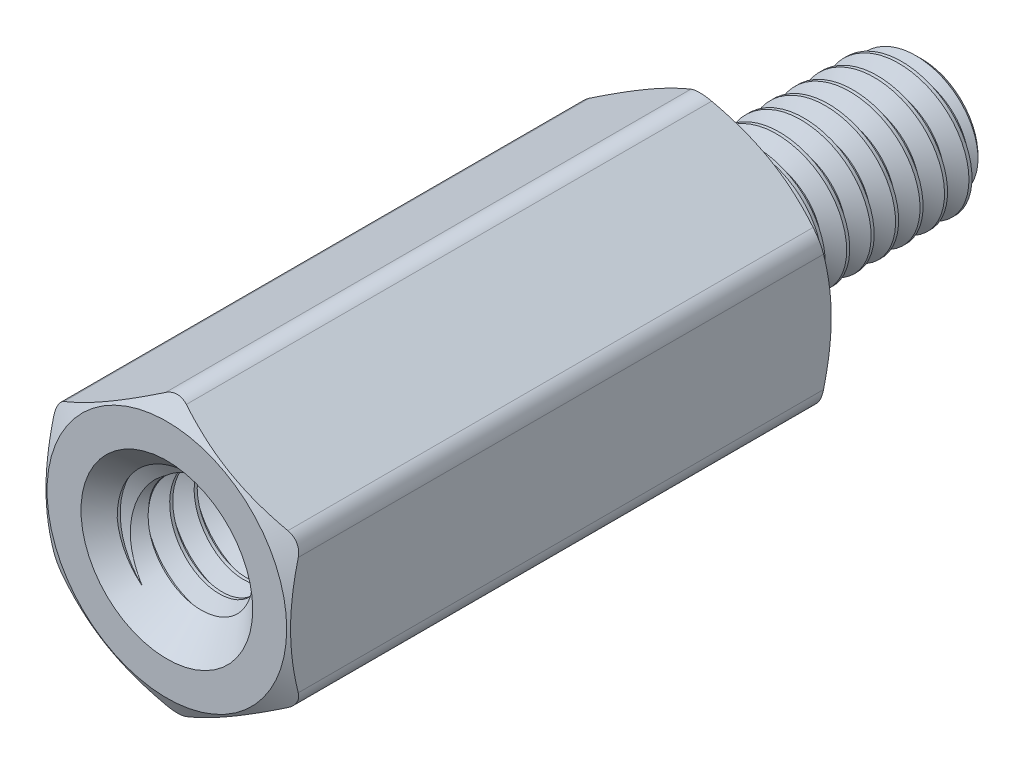
SolidWorks part; units mm, degrees
ref_plane "Front Plane" through (0, 0, 0) normal (0, 0, 1) x (1, 0, 0)
ref_plane "Top Plane" through (0, 0, 0) normal (0, 1, 0) x (1, 0, 0)
ref_plane "Right Plane" through (0, 0, 0) normal (1, 0, 0) x (0, 0, -1)
sketch "Sketch1" plane through (0, 0, 0) normal (0, 0, 1) x (1, 0, 0)
  line L1 (2.25, 1.299) -> (0, 2.5981)
  line L2 (0, 2.5981) -> (-2.25, 1.299)
  line L3 (-2.25, 1.299) -> (-2.25, -1.299)
  line L4 (-2.25, -1.299) -> (0, -2.5981)
  line L5 (0, -2.5981) -> (2.25, -1.299)
  line L6 (2.25, -1.299) -> (2.25, 1.299)
  circle A0 centre (0, 0) radius 2.25 construction
  point P10 (0, -2.25)
  dimension "Hex Size" = 4.5
sketch "Sketch2" plane through (0, 0, 0) normal (1, 0, 0) x (0, 0, -1)
  line L0 (3.9, 0) -> (-10, 0) construction
  line L2 (0, 1.25) -> (0, -1.25) construction
  line L3 (-5.2, 1.25) -> (-5.2, -1.25) construction
  line L4 (-10.4219, 1.2987) -> (-10.1969, 0.909) construction
  line L5 (-10.1969, 0.909) -> (-9.9719, 1.2987) construction
  line L6 (-9.9719, 1.2987) -> (-10.4219, 1.2987) construction
  line L7 (-10.3938, 1.25) -> (-10, 1.25) construction
  line L8 (-10.225, 0.9577) -> (-10.1688, 0.9577) construction
  line L9 (-10.1969, 0.9577) -> (-10.1969, 0.909) construction
  line L10 (-10.1969, 1.25) -> (-10.1969, 1.2987) construction
  line L11 (3.8719, 1.2987) -> (4.3219, 1.2987) construction
  line L12 (4.3219, 1.2987) -> (4.0969, 0.909) construction
  line L13 (4.0969, 0.909) -> (3.8719, 1.2987) construction
  line L14 (3.9, 1.25) -> (4.2937, 1.25) construction
  line L15 (4.0687, 0.9577) -> (4.125, 0.9577) construction
  line L16 (4.0969, 0.9577) -> (4.0969, 0.909) construction
  line L17 (4.0969, 1.25) -> (4.0969, 1.2987) construction
  line L18 (0, 2.5981) -> (-10, 2.5981) construction
  point P6 (0, 0)
  point P9 (-5.2, 0)
  dimension "Length" = 10
sketch "Sketch3" plane through (0, 0, 0) normal (1, 0, 0) x (0, 0, -1)
  line L0 (-5.2, 0) -> (3.9, 0)
  line L1 (-5.2, 1.25) -> (-5.2, -1.25) construction
  line L2 (3.9, 0) -> (3.9, 1.025)
  line L3 (3.9, 1.025) -> (3.675, 1.25)
  line L4 (3.675, 1.25) -> (0.6367, 1.25)
  line L5 (0.6367, 1.25) -> (0.468, 0.9577)
  line L6 (-5.2, 0) -> (-5.2, 1.025)
  line L7 (-5.2, 1.025) -> (-5.425, 1.25)
  line L8 (-5.425, 1.25) -> (-9.775, 1.25)
  line L9 (-9.775, 1.25) -> (-10, 1.475)
  line L10 (3.675, 0) -> (3.675, -1.25) construction
  line L11 (-10, 1.475) -> (-10, 2.25)
  line L12 (-10, 2.25) -> (0, 2.25)
  line L14 (0.468, 0.9577) -> (0.225, 0.9577)
  line L15 (0, 1.1827) -> (0, 2.25)
  arc A0 (0, 1.1827) -> (0.225, 0.9577) centre (0.225, 1.1827) ccw
  point P5 (-10, -2.25)
  point P8 (-8.875, -1.25)
  point P9 (2.775, -1.25)
  point P27 (0, 0.9577)
  dimension "D4" = 0.225
  dimension "D2" = 0.225
  dimension "D1" = 45
  dimension "D6" = 1.125
  dimension "D7" = 60
  dimension "D3" = 1.125
  dimension "D5" = 0.468
revolve "Revolve1" add sketch "Sketch3" angle 360 about L0 region at (0, 1.1513, 2.7085)
sketch "Sketch4" plane through (0, 0, 10) normal (0, 0, 1) x (1, 0, 0)
  line L0 (0, 2.25) -> (0, 1.25) construction
  line L1 (-2.25, 1.299) -> (-2.25, -1.299)
  line L2 (-2.25, -1.299) -> (0, -2.5981)
  line L3 (0, -2.5981) -> (2.25, -1.299)
  line L4 (2.25, -1.299) -> (2.25, 1.299)
  line L5 (2.25, 1.299) -> (0, 2.5981)
  line L6 (0, 2.5981) -> (-2.25, 1.299)
  circle A0 centre (0, 0) radius 2.25 construction
  circle A1 centre (0, 0) radius 1.75
  circle A2 centre (0, 0) radius 2.25 construction
  point P16 (0, 1.75)
extrude "Boss-Extrude1" add sketch "Sketch4" against normal up to surface (10 mm away) up to face at (0, 2.25, 0)
sketch "Sketch5" plane through (0, 0, 10) normal (0, 0, 1) x (1, 0, 0)
  line L0 (-0.717, 1.0239) -> (0.717, -1.0239) construction
  line L1 (0, 1.25) -> (0, -1.25) construction
  line L3 (0, -2.7928) -> (0, 2.7928) construction
  circle A0 centre (0, 0) radius 2.205
  point P11 (0.717, -1.0239)
  dimension "D1" = 4.41
  dimension "D2" = 35
extrude "Cut-Extrude1" cut sketch "Sketch5" against normal through all draft 60 flip side to cut
sketch "Sketch6" plane through (0, 0, 0) normal (0, 0, -1) x (-1, 0, 0)
  circle A0 centre (0, 0) radius 2.205
  circle A1 centre (0, 0) radius 2.205 construction
extrude "Cut-Extrude2" cut sketch "Sketch6" against normal through all draft 60 flip side to cut
fillet "Fillet1" radius 0.3825 6 edges at (0, 2.5981, 5) (-2.25, -1.299, 5) (0, -2.5981, 5) (2.25, -1.299, 5) (2.25, 1.299, 5) (-2.25, 1.299, 5)
sketch "Drawing1" plane through (0, 0, 0) normal (1, 0, 0) x (0, 0, -1)
  line L0 (-10, 1.25) -> (-5.2, 1.25) construction
  line L1 (-5.2, 1.25) -> (-5.2, -1.25) construction
  line L2 (-5.2, -1.25) -> (-10, -1.25) construction
sketch "Sketch7" plane through (0, 0, 0) normal (-1, 0, 0) x (0, 0, 1)
  line L0 (-4.0687, 0.9577) -> (-4.125, 0.9577)
  line L1 (-4.125, 0.9577) -> (-4.3078, 1.2744)
  line L2 (-4.3219, 1.2987) -> (-4.0969, 0.909) construction
  line L3 (-4.3078, 1.2744) -> (-3.8859, 1.2744)
  line L4 (-4.0969, 0.909) -> (-3.8719, 1.2987) construction
  line L5 (-3.8859, 1.2744) -> (-4.0687, 0.9577)
  line L6 (-4.0969, 1.25) -> (-4.0969, 1.2987) construction
  point P12 (-4.0969, 1.2744)
sketch "Sketch8" plane through (0, 0, -3.9) normal (0, 0, -1) x (-1, 0, 0)
  circle A0 centre (0, 0) radius 1.25
curve "Helix/Spiral1" pitch 0.45 height 3.783 radius 1.25 centre (0, 0, -3.9) axis (0, 0, 1) start towards (0, 1, 0)
sweep "Cut-Sweep1" cut profiles "Sketch7" path "Helix/Spiral1" align with end faces yes
sketch "Sketch9" plane through (0, 0, 5.2) normal (0, 0, 1) x (1, 0, 0)
  circle A0 centre (0, 0) radius 1.475
extrude "Boss-Extrude2" add sketch "Sketch9" along normal up to surface (4.8 mm away) up to face at (0, 1.475, 10)
sketch "Sketch10" plane through (0, 0, 0) normal (1, 0, 0) x (0, 0, -1)
  line L0 (3.9, 0) -> (-10, 0) construction
  line L1 (-5.2, 1.25) -> (-10, 1.25)
  line L2 (-5.2, 1.25) -> (-5.2, 0)
  line L3 (-5.2, 0) -> (-10, 0)
  line L4 (-10, 1.25) -> (-10, 0)
revolve "Revolve2" add sketch "Sketch10" angle 360 about L0
sketch "Sketch11" plane through (0, 0, 10) normal (0, 0, 1) x (1, 0, 0)
  circle A0 centre (0, 0) radius 1.25
  circle A1 centre (0, 0) radius 1.25 construction
sketch "Sketch12" plane through (0, 0, 0) normal (1, 0, 0) x (0, 0, -1)
  line L0 (-10.225, 0.9577) -> (-10.1688, 0.9577)
  line L1 (-10.1688, 0.9577) -> (-9.9859, 1.2744)
  line L2 (-10.1969, 0.909) -> (-9.9719, 1.2987) construction
  line L3 (-9.9859, 1.2744) -> (-10.4078, 1.2744)
  line L4 (-10.4219, 1.2987) -> (-10.1969, 0.909) construction
  line L5 (-10.4078, 1.2744) -> (-10.225, 0.9577)
  line L6 (-10.1969, 1.25) -> (-10.1969, 1.2987) construction
  point P12 (-10.1969, 1.2744)
curve "Helix/Spiral2" pitch 0.45 height 5.25 radius 1.25 centre (0, 0, 10) axis (0, 0, -1) start towards (0, 1, 0)
sweep "Cut-Sweep2" cut profiles "Sketch12" path "Helix/Spiral2" align with end faces yes
combine bodies "Combine1" operation type subtract main body 113 bodies to subtract 114
sketch "Sketch13" plane through (0, 0, 10) normal (0, 0, 1) x (1, 0, 0)
  circle A0 centre (0, 0) radius 1.58
  dimension "D1" = 3.16
extrude "Cut-Extrude3" cut sketch "Sketch13" against normal through all draft 45
equation "\"Thread Pitch (B)/8@Sketch2\" = \"Thread Pitch (B)@Sketch2\" / 8"
equation "\"Thread Pitch (A)/8@Sketch2\" = \"Thread Pitch (A)@Sketch2\" / 8"
equation "\"D1@Sketch5\"=\"Hex Size@Sketch1\" * .98"
equation "\"D1@Fillet1\"=\"Hex Size@Sketch1\" * .085"
equation "\"D2@Sketch3\"=\"Thread Pitch (A)@Sketch2\" * .5"
equation "\"D4@Sketch3\" = \"D2@Sketch3\""
equation "\"D6@Sketch3\" = \"Thread Pitch (A)@Sketch2\" * 2.5"
equation "\"D3@Helix/Spiral1\" = \"Thread Length (A)@Sketch2\" - \"D5@Sketch3\" * .25"
equation "\"D4@Helix/Spiral1\" = \"Thread Pitch (A)@Sketch2\""
equation "\"D3@Sketch3\" = \"Thread Pitch (B)@Sketch2\" * 2.5"
equation "\"D5@Sketch3\" = \"Thread Length (A)@Sketch2\" * .12"
equation "\"D3@Helix/Spiral2\" = \"Minimum Thread Length (B)@Sketch2\" + \"Thread Pitch (B)@Sketch2\""
equation "\"D4@Helix/Spiral2\" = \"Thread Pitch (B)@Sketch2\""
equation "\"D1@Sketch13\"=(\"Hex Size@Sketch1\"-\"Thread Size (A)@Sketch2\")*.33+\"Thread Size (A)@Sketch2\""
